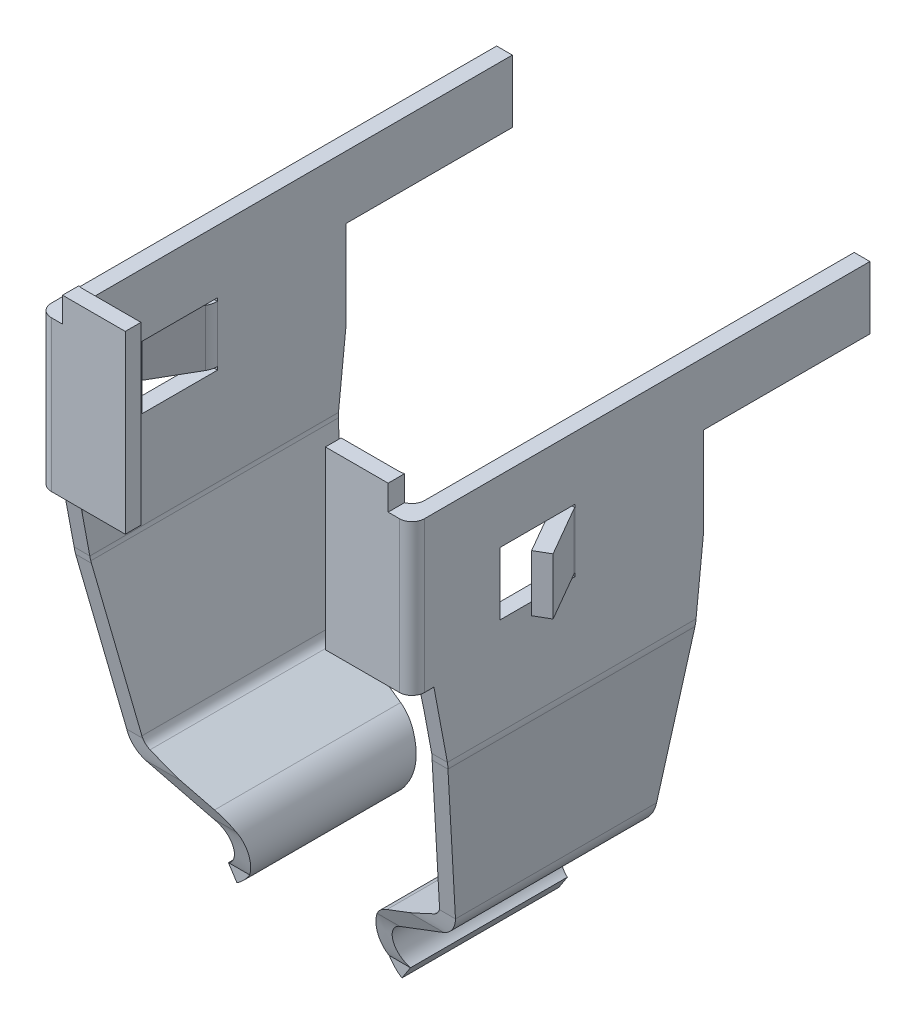
SolidWorks part; units mm, degrees
ref_plane "Front Plane" through (0, 0, 0) normal (0, 0, 1) x (1, 0, 0)
ref_plane "Top Plane" through (0, 0, 0) normal (0, 1, 0) x (1, 0, 0)
ref_plane "Right Plane" through (0, 0, 0) normal (1, 0, 0) x (0, 0, -1)
sketch "Szkic1" plane through (0, 0, 0) normal (0, 0, 1) x (1, 0, 0)
  line L0 (1.4051, 4.2043) -> (1.0572, 1.7286)
  line L1 (1.3048, 1.6939) -> (1.6527, 4.1695)
  line L2 (0.9499, 1.5783) -> (0.0589, 1.1243)
  line L3 (0.1724, 0.9015) -> (1.0634, 1.3555)
  line L4 (0, 0) -> (0.1362, 0.2097)
  line L5 (1.41, 5.4215) -> (1.41, 4.2739)
  line L6 (1.66, 4.2739) -> (1.66, 5.4215)
  line L7 (1.66, 5.4215) -> (1.66, 7.8215)
  line L8 (1.66, 7.8215) -> (1.41, 7.8215)
  line L9 (1.41, 7.8215) -> (1.41, 5.4215)
  arc A0 (1.4051, 4.2043) -> (1.41, 4.2739) centre (0.91, 4.2739) ccw
  arc A1 (1.6527, 4.1695) -> (1.66, 4.2739) centre (0.91, 4.2739) ccw
  arc A2 (0.9499, 1.5783) -> (1.0572, 1.7286) centre (0.8591, 1.7565) ccw
  arc A3 (1.0634, 1.3555) -> (1.3048, 1.6939) centre (0.8591, 1.7565) ccw
  arc A4 (0.0589, 1.1243) -> (0, 0) centre (0.354, 0.5451) ccw
  arc A5 (0.1724, 0.9015) -> (0.1362, 0.2097) centre (0.354, 0.5451) ccw
extrude "Dodanie-wyciągnięcie1" add sketch "Szkic1" along normal blind 7.3
sketch "Szkic2" plane through (0, 0, 7.3) normal (0, 0, 1) x (1, 0, 0)
  line L0 (1.3552, 5.4215) -> (1.6552, 5.4215)
  line L1 (1.6552, 5.4215) -> (1.6552, 7.8215)
  line L2 (1.6552, 7.8215) -> (1.3552, 7.8215)
  line L3 (1.2802, 8.2215) -> (0.2802, 8.2215)
  line L4 (0.2802, 8.2215) -> (0.2802, 5.4215)
  line L5 (0.2802, 5.4215) -> (1.3552, 5.4215)
  line L6 (1.3552, 7.8215) -> (1.2802, 7.8215)
  line L7 (1.2802, 7.8215) -> (1.2802, 8.2215)
extrude "Dodanie-wyciągnięcie2" add sketch "Szkic2" against normal blind 0.25
sketch "Szkic5" plane through (1.66, 0, 0) normal (1, 0, 0) x (0, 0, -1)
  line L23 (-5.8, 0) -> (-3.3, 0)
  line L24 (-3.3, 0) -> (-3.3, 0.2097)
  line L25 (-5.8, 0.2097) -> (-5.8, 0)
  line L26 (-3.1837, 0.9015) -> (-3.078, 1.3555)
  line L27 (-6.1928, 1.3555) -> (-6.0057, 0.9015)
  line L28 (-3.045, 1.6939) -> (-2.7806, 4.1695)
  line L29 (-6.719, 4.1695) -> (-6.2512, 1.6939)
  line L30 (-7.3, 5.4215) -> (-7, 5.4215)
  line L31 (-7, 7.8215) -> (-7.3, 7.8215)
  line L32 (-7.3, 7.8215) -> (-7.3, 5.4215)
  line L33 (-2.65, 5.4215) -> (-2.65, 6.8215)
  line L34 (-2.65, 6.8215) -> (0, 6.8215)
  line L35 (0, 6.8215) -> (0, 7.8215)
  line L36 (0, 7.8215) -> (-7, 7.8215)
  line L37 (-7, 5.4215) -> (-6.95, 5.4215)
  line L38 (-6.95, 5.4215) -> (-6.7353, 4.2739)
  line L39 (-2.7714, 4.2739) -> (-2.65, 5.4215)
  line L40 (-4.7, 6.8215) -> (-4.7, 6.7715)
  line L41 (-4.7, 5.8715) -> (-4.7, 5.8215)
  line L42 (-4.7, 6.7715) -> (-4.7, 5.8715)
  line L43 (-4.7, 5.8215) -> (-5.9, 5.8215)
  line L44 (-5.9, 6.8215) -> (-4.7, 6.8215)
  line L45 (-5.9, 5.8215) -> (-5.9, 6.8215)
  line L46 (-7.3, 5.4215) -> (-10.0524, -0.1744)
  line L47 (-10.0524, -0.1744) -> (-7, -1.8423)
  line L48 (-7, -1.8423) -> (-5.8, 0)
  line L49 (-3.3, 0) -> (0.6775, -1.8423)
  line L50 (0.6775, -1.8423) -> (2.0576, 3.6528)
  line L51 (2.0576, 3.6528) -> (0, 6.8215)
  spline S0 degree 3 poles (-6.0057, 0.9015) (-6.0007, 0.8922) (-5.9956, 0.8813) (-5.9854, 0.8571) (-5.9804, 0.8437) (-5.9702, 0.8146) (-5.9651, 0.7989) (-5.955, 0.7657) (-5.9499, 0.7481) (-5.9398, 0.7114) (-5.9347, 0.6923) (-5.9296, 0.6728) (-5.9271, 0.663) (-5.9246, 0.6531) (-5.922, 0.6431) (-5.917, 0.6231) (-5.9119, 0.6026) (-5.9017, 0.5615) (-5.8967, 0.5408) (-5.8916, 0.5202) (-5.8891, 0.5099) (-5.8865, 0.4996) (-5.884, 0.4894) (-5.8789, 0.469) (-5.8738, 0.4487) (-5.8637, 0.4092) (-5.8586, 0.3899) (-5.8536, 0.3713) (-5.851, 0.362) (-5.8485, 0.3529) (-5.846, 0.344) (-5.8409, 0.3262) (-5.8358, 0.3091) (-5.8257, 0.2771) (-5.8206, 0.262) (-5.8104, 0.2341) (-5.8052, 0.2212) (-5.8, 0.2097) knots 0 0 0 0 0.000064 0.000064 0.000128 0.000128 0.000191 0.000191 0.000255 0.000255 0.000319 0.000319 0.000319 0.000351 0.000351 0.000351 0.000414 0.000414 0.000478 0.000478 0.000478 0.00051 0.00051 0.00051 0.000574 0.000574 0.000637 0.000637 0.000637 0.000669 0.000669 0.000669 0.000733 0.000733 0.000797 0.000797 0.000862 0.000862 0.000862 0.000862
  spline S1 degree 3 poles (-3.3, 0.2097) (-3.2903, 0.2477) (-3.2806, 0.3013) (-3.2612, 0.4257) (-3.2515, 0.4964) (-3.2322, 0.6358) (-3.2225, 0.7044) (-3.2031, 0.8215) (-3.1934, 0.8698) (-3.1837, 0.9015) knots 0 0 0 0 0.25 0.25 0.5 0.5 0.75 0.75 1 1 1 1
  spline S2 degree 3 poles (-3.078, 1.3555) (-3.0669, 1.4215) (-3.0561, 1.55) (-3.045, 1.6939) knots 0 0 0 0 1 1 1 1
  spline S3 degree 3 poles (-6.2512, 1.6939) (-6.2316, 1.55) (-6.2125, 1.4215) (-6.1928, 1.3555) knots 0 0 0 0 1 1 1 1
  spline S4 degree 3 poles (-2.7806, 4.1695) (-2.7775, 4.2041) (-2.7744, 4.239) (-2.7714, 4.2739) knots 0 0 0 0 1 1 1 1
  spline S5 degree 3 poles (-6.7353, 4.2739) (-6.7326, 4.2564) (-6.7298, 4.2389) (-6.7244, 4.2041) (-6.7217, 4.1868) (-6.719, 4.1695) knots 0 0 0 0 0.000053 0.000053 0.000106 0.000106 0.000106 0.000106
  line M30 (0, 4.2739) -> (0, 7.8215)
  line M32 (-7.3, 7.8215) -> (-7.3, 4.2739)
  line M33 (-7.3, 4.2739) -> (0, 4.2739)
extrude "Wytnij-wyciągnięcie2" cut sketch "Szkic5" against normal through all contours L45 L43 L41 L42 L40 L44 | S4 L28 S2 L26 S1 L24 L49 L50 L51 M30 M33 | S5 L46 L47 L48 L25 S0 L27 S3 L29 M33 M32 region at (1.66, 1.1572, 7.6708) region at (1.66, 1.9649, 0.5555) region at (1.66, 6.3215, 5.3)
extrude "Wytnij-wyciągnięcie3" cut sketch "Szkic5<5>" against normal through all contours L38 L37 L30 M32 M33 | L39 L34 L33 M33 M30 region at (1.66, 4.8028, 7.0671) region at (1.66, 5.5386, 1.3389)
sketch "Szkic5<5>" plane through (1.66, 0, 0) normal (1, 0, 0) x (0, 0, -1) same geometry as "Szkic5"
fillet "Zaokrąglenie1" radius 0.2 1 edges at (1.66, 6.6215, 7.3)
fillet "Zaokrąglenie2" radius 0.2 1 edges at (1.41, 6.6215, 7.05)
sketch "Szkic6" plane through (0, 5.8215, 0) normal (0, 1, 0) x (1, 0, 0)
  line L0 (1.66, -4.7) -> (1.41, -4.7)
  line L1 (2.1209, -5.5117) -> (1.6667, -4.725)
  line L2 (1.9044, -5.6367) -> (2.1209, -5.5117)
  line L3 (1.4502, -4.85) -> (1.9044, -5.6367)
  arc A0 (1.41, -4.7) -> (1.4502, -4.85) centre (1.71, -4.7) ccw
  arc A1 (1.66, -4.7) -> (1.6667, -4.725) centre (1.71, -4.7) ccw
extrude "Dodanie-wyciągnięcie3" add sketch "Szkic6" along normal blind 0.9 from offset 0.05
ref_plane "Płaszczyzna2" through (-1.315, 0, 0) normal (-1, 0, 0) x (0, 0, 1)
mirror "Lustro2" about plane through (-1.315, 0, 0) normal (-1, 0, 0) of bodies 105
